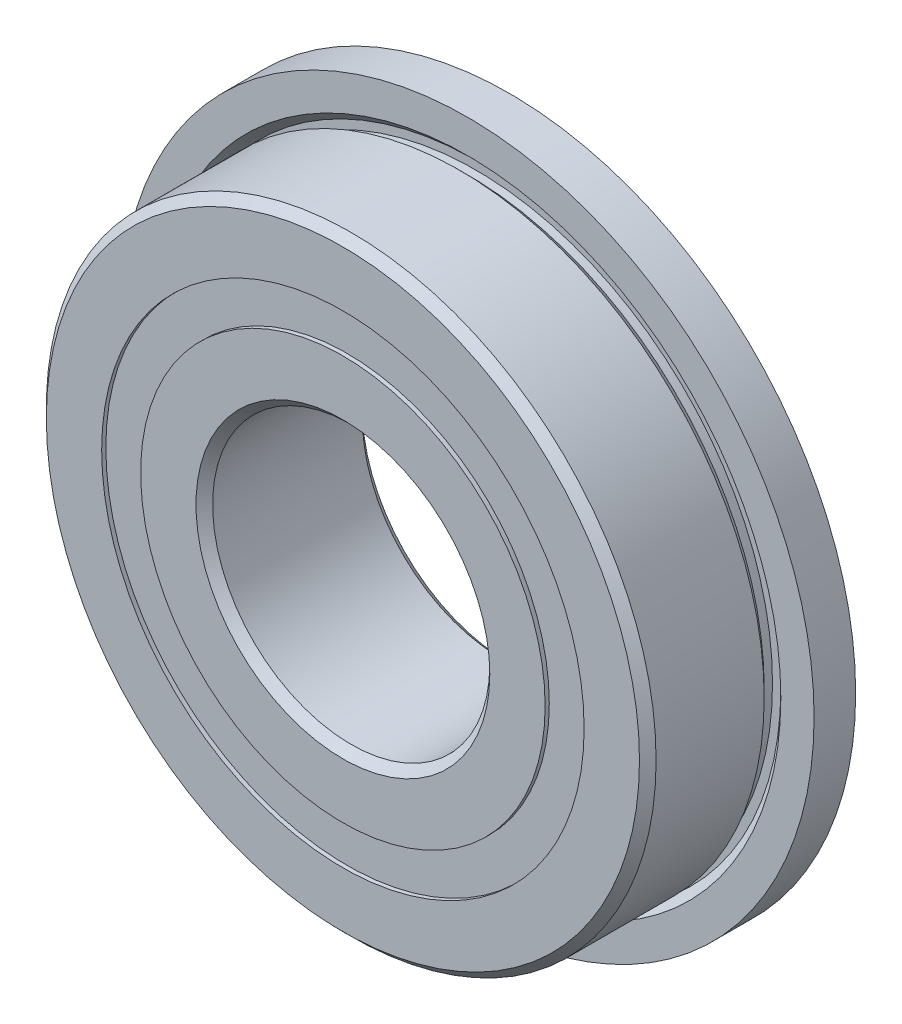
SolidWorks part; units mm, degrees
material "Chrome Stainless Steel"
ref_plane "Front Plane" through (0, 0, 0) normal (0, 0, 1) x (1, 0, 0)
ref_plane "Top Plane" through (0, 0, 0) normal (0, 1, 0) x (1, 0, 0)
ref_plane "Right Plane" through (0, 0, 0) normal (1, 0, 0) x (0, 0, -1)
sketch "Sketch1" plane through (0, 0, 0) normal (0, 0, 1) x (1, 0, 0)
  circle A0 centre (0, 0) radius 5
  dimension "ID" = 10
sketch "Sketch2" plane through (0, 0, 0) normal (1, 0, 0) x (0, 0, -1)
  line L0 (-3, 0) -> (3, 0) construction
  line L1 (0, 11) -> (0, -11) construction
  line L2 (2.7, 11) -> (-2.7, 11) construction
  line L3 (-2.7, 11) -> (-3, 10.7)
  line L4 (-3, 10.7) -> (-3, 8.7033)
  line L5 (-3, 8.7033) -> (-1.3333, 8.7033)
  line L6 (3, 8.7033) -> (1.3333, 8.7033)
  line L7 (3, 10.7) -> (3, 8.7033)
  line L8 (2.7, 11) -> (3, 10.7) construction
  line L9 (0, 11) -> (0, 8) construction
  line L10 (0, 8) -> (0, 5) construction
  line L11 (1.5, 0) -> (1.5, 11) construction
  line L12 (3, 10.7) -> (3, 12.5)
  line L13 (3, 12.5) -> (1.5, 12.5)
  line L14 (1.5, 12.5) -> (1.5, 11.3)
  line L15 (1.5, 11.3) -> (1.8, 11)
  line L16 (1.8, 11) -> (1.8, 10.7)
  line L17 (1.8, 10.7) -> (1.5, 10.7)
  line L18 (1.5, 10.7) -> (1.2, 11)
  line L19 (-2.7, 11) -> (1.2, 11)
  line L20 (3, 12.5) -> (3, -12.5) construction
  line L21 (1.5, 11) -> (1.5, 11.3) construction
  line L22 (1.5, 11) -> (1.2, 11) construction
  line L23 (0, 5) -> (0, -5) construction
  arc A0 (-1.3333, 8.7033) -> (1.3333, 8.7033) centre (0, 8) cw
  point P14 (0, 5)
  point P15 (1.5, 0)
  point P25 (3, 0)
  point P29 (-2.7, -11)
  dimension "D1" = 45
  dimension "D2" = 0.3
  dimension "D3" = 2.6667
  dimension "D4" = 0.7033
  dimension "Flange Thickness" = 1.5
  dimension "Flange OD" = 25
  dimension "Width" = 6
  dimension "OD" = 22
sketch "Sketch7" plane through (0, 0, 0) normal (1, 0, 0) x (0, 0, -1)
  line L13 (3, 12.5) -> (1.5, 12.5)
  line L14 (1.5, 12.5) -> (1.5, 11.3)
  line L15 (1.5, 11.3) -> (1.8, 11)
  line L16 (1.8, 11) -> (1.8, 10.7)
  line L17 (1.8, 10.7) -> (1.5, 10.7)
  line L18 (1.5, 10.7) -> (1.2, 11)
  line L19 (1.2, 11) -> (-2.7, 11)
  line L20 (-2.7, 11) -> (-3, 10.7)
  line L21 (-3, 10.7) -> (-3, 8.7033)
  line L22 (-3, 8.7033) -> (-1.3333, 8.7033)
  line L23 (1.3333, 8.7033) -> (3, 8.7033)
  line L24 (3, 8.7033) -> (3, 10.7)
  line L25 (3, 10.7) -> (3, 12.5)
  line L26 (3, 12.5) -> (1.5, 12.5)
  line L27 (1.5, 12.5) -> (1.5, 11.3)
  line L28 (1.5, 11.3) -> (1.8, 11)
  line L29 (1.8, 11) -> (1.8, 10.7)
  line L30 (1.8, 10.7) -> (1.5, 10.7)
  line L31 (1.5, 10.7) -> (1.2, 11)
  line L32 (1.2, 11) -> (-2.7, 11)
  line L33 (-2.7, 11) -> (-3, 10.7)
  line L34 (-3, 10.7) -> (-3, 8.7033)
  line L35 (-3, 8.7033) -> (-1.3333, 8.7033)
  line L36 (1.3333, 8.7033) -> (3, 8.7033)
  line L37 (3, 8.7033) -> (3, 10.7)
  line L38 (3, 10.7) -> (3, 12.5)
  arc A1 (1.3333, 8.7033) -> (-1.3333, 8.7033) centre (0, 8) ccw
  arc A2 (1.3333, 8.7033) -> (-1.3333, 8.7033) centre (0, 8) ccw
  dimension "D1" = 0
revolve "Revolve7" add sketch "Sketch7" angle 360 about L0
sketch "Sketch3" plane through (0, 0, 0) normal (1, 0, 0) x (0, 0, -1)
  line L0 (-3, 7.2967) -> (-1.3333, 7.2967)
  line L1 (0, 11) -> (0, -11) construction
  line L2 (-3, 10.7) -> (-3, 8.7033) construction
  line L3 (-3, 7.2967) -> (-3, 5.3)
  line L4 (-2.7, 11) -> (-3, 10.7) construction
  line L5 (-3, 5.3) -> (-2.7, 5)
  line L6 (-2.7, 5) -> (2.7, 5)
  line L8 (2.7, 5) -> (3, 5.3)
  line L10 (3, 5.3) -> (3, 7.2967)
  line L11 (3, 7.2967) -> (1.3333, 7.2967)
  line L13 (2.7, 11) -> (3, 10.7) construction
  arc A0 (1.3333, 8.7033) -> (-1.3333, 8.7033) centre (0, 8) ccw construction
  arc A1 (1.3333, 7.2967) -> (-1.3333, 7.2967) centre (0, 8) cw
revolve "Revolve3" add sketch "Sketch3" angle 360 about L0
sketch "Sketch6" plane through (0, 0, 0) normal (1, 0, 0) x (0, 0, -1)
  line L1 (-0.1172, 8.3516) -> (0.1172, 8.3516)
  line L2 (-0.1172, 8.3516) -> (-0.1172, 7.6484)
  line L3 (-0.1172, 7.6484) -> (0.1172, 7.6484)
  line L4 (0.1172, 8.3516) -> (0.1172, 7.6484)
  line L5 (-0.1172, 8.3516) -> (0.1172, 7.6484) construction
  line L6 (-0.1172, 7.6484) -> (0.1172, 8.3516) construction
  point P4 (0, 8)
  dimension "D1" = 0.7033
  dimension "D2" = 0.2344
revolve "Revolve6" add sketch "Sketch6" angle 360 about L0
sketch "Sketch4" plane through (0, 0, 0) normal (1, 0, 0) x (0, 0, -1)
  line L0 (-1.5074, 8) -> (1.5074, 8)
  arc A2 (-1.5074, 8) -> (1.5074, 8) centre (0, 8) cw
  arc A3 (1.3333, 8.7033) -> (-1.3333, 8.7033) centre (0, 8) ccw construction
revolve "Revolve4" add sketch "Sketch4" angle 360 about L0
ref_axis "Axis1" through (0, 0, -3) along (0, 0, 1)
pattern_circular "CirPattern1" [suppressed] count 10 over 360 about axis through (0, 0, -3) along (0, 0, 1) of bodies 104
sketch "Sketch5" plane through (0, 0, 0) normal (1, 0, 0) x (0, 0, -1)
  line L0 (-3, 8.7033) -> (-1.3333, 8.7033) construction
  line L1 (-2.85, 8.7033) -> (-1.5074, 8.7033)
  line L2 (-2.85, 8.7033) -> (-2.85, 7.2967)
  line L3 (-2.85, 7.2967) -> (-1.5074, 7.2967)
  line L4 (-1.5074, 8.7033) -> (-1.5074, 7.2967)
  line L5 (-3, 7.2967) -> (-1.3333, 7.2967) construction
  line L6 (3, 8.7033) -> (1.3333, 8.7033) construction
  line L7 (2.85, 8.7033) -> (1.5074, 8.7033)
  line L8 (2.85, 8.7033) -> (2.85, 7.2967)
  line L9 (2.85, 7.2967) -> (1.5074, 7.2967)
  line L10 (1.5074, 8.7033) -> (1.5074, 7.2967)
  line L11 (3, 7.2967) -> (1.3333, 7.2967) construction
  line L12 (-2.7, 11) -> (-3, 10.7) construction
  point P18 (-2.85, 10.85)
revolve "Revolve5" add sketch "Sketch5" angle 360 about L0
equation "\"D2@Sketch2\" = \"Width@Sketch2\" * .05"
equation "\"D3@Sketch2\" = \"Width@Sketch2\" / 2.25"
equation "\"D4@Sketch2\" =  (  (  ( \"OD@Sketch2\" - \"Width@Sketch2\" )  / 2 )  / 3.25 )  / 3.5"
equation "\"D2@CirPattern1\" = 360/\"Balls@CirPattern1\""
equation "\"D1@Sketch6\" = \"D4@Sketch2\""
equation "\"D2@Sketch6\"=\"D1@Sketch6\"/3"
